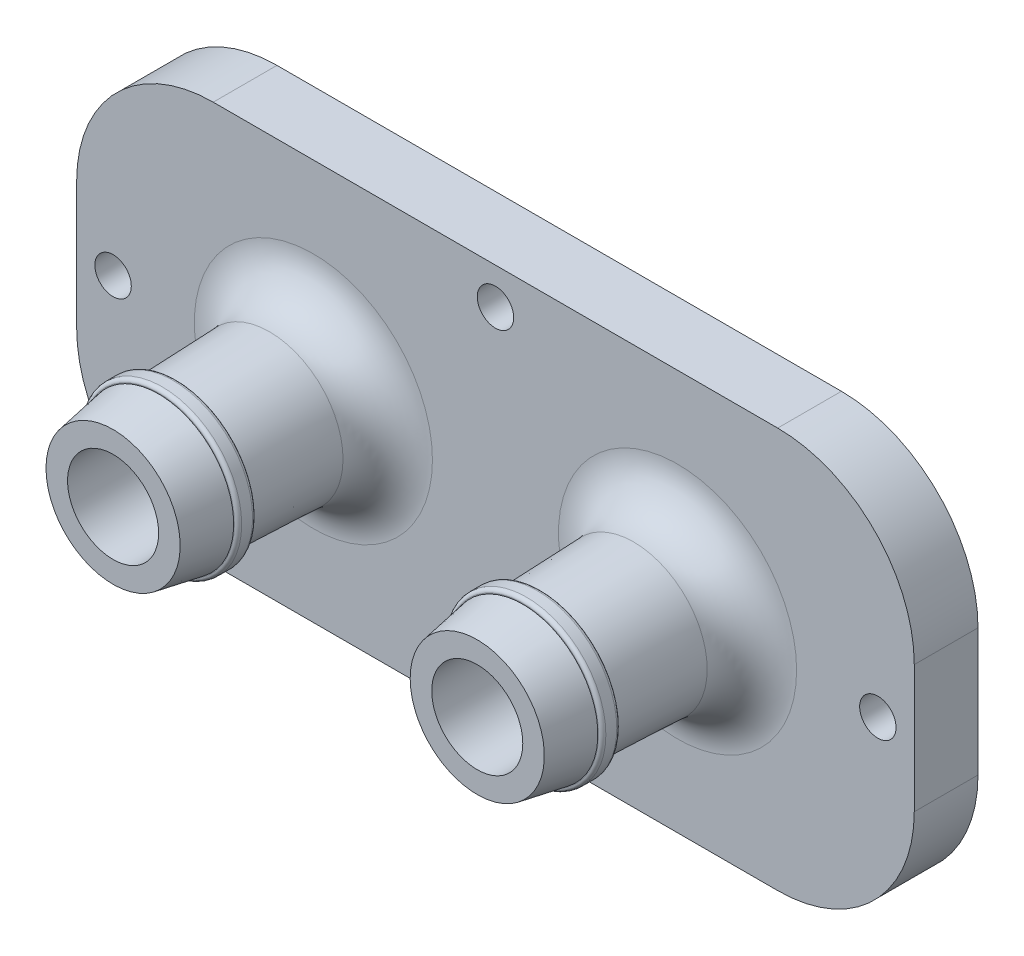
SolidWorks part; units mm, degrees
ref_plane "Front Plane" through (0, 0, 0) normal (0, 0, 1) x (1, 0, 0)
ref_plane "Top Plane" through (0, 0, 0) normal (0, 1, 0) x (1, 0, 0)
ref_plane "Right Plane" through (0, 0, 0) normal (1, 0, 0) x (0, 0, -1)
sketch "Sketch1" plane through (0, 0, 0) normal (0, 0, 1) x (1, 0, 0)
  line L0 (-38.0465, 0) -> (47.5349, 0) construction
  line L1 (0, 0) -> (0, 26.093) construction
  line L3 (-46, 22) -> (46, 22)
  line L4 (-46, 22) -> (-46, -22)
  line L5 (-46, -22) -> (46, -22)
  line L6 (46, 22) -> (46, -22)
  circle A0 centre (20, 0) radius 17
  circle A1 centre (-20, 0) radius 17
  point P9 (0, 0)
  point P14 (0, 0)
  dimension "D2" = 34
  dimension "D1" = 40
  dimension "D3" = 26
  dimension "D4" = 22
extrude "Boss-Extrude1" add sketch "Sketch1" along normal blind 4
fillet "Fillet1" radius 15 4 edges at (-46, -22, 2) (46, -22, 2) (46, 22, 2) (-46, 22, 2)
sketch "Sketch2" plane through (0, 0, 4) normal (0, 0, 1) x (1, 0, 0)
  line L8 (-46, 7) -> (-46, -7)
  line L9 (-31, -22) -> (31, -22)
  line L10 (46, -7) -> (46, 7)
  line L11 (31, 22) -> (-31, 22)
  line L12 (-46, 7) -> (-46, -7)
  line L13 (-31, -22) -> (31, -22)
  line L14 (46, -7) -> (46, 7)
  line L15 (31, 22) -> (-31, 22)
  circle A4 centre (-20, 0) radius 5
  circle A5 centre (-20, 0) radius 17 construction
  circle A6 centre (20, 0) radius 5
  circle A7 centre (20, 0) radius 17 construction
  arc A8 (-31, 22) -> (-46, 7) centre (-31, 7) ccw
  arc A9 (-46, -7) -> (-31, -22) centre (-31, -7) ccw
  arc A10 (31, -22) -> (46, -7) centre (31, -7) ccw
  arc A11 (46, 7) -> (31, 22) centre (31, 7) ccw
  arc A12 (-31, 22) -> (-46, 7) centre (-31, 7) ccw
  arc A13 (-46, -7) -> (-31, -22) centre (-31, -7) ccw
  arc A14 (31, -22) -> (46, -7) centre (31, -7) ccw
  arc A15 (46, 7) -> (31, 22) centre (31, 7) ccw
  dimension "D2" = 10
  dimension "D1" = 0
extrude "Boss-Extrude2" add sketch "Sketch2" along normal blind 3
sketch "Sketch3" plane through (0, 0, 7) normal (0, 0, 1) x (1, 0, 0)
  circle A0 centre (-20, 0) radius 7.25
  circle A1 centre (20, 0) radius 7.25
  circle A2 centre (20, 0) radius 5
  circle A3 centre (-20, 0) radius 5
  circle A4 centre (-20, 0) radius 5 construction
  point P9 (-20, -0.8455)
  dimension "D1" = 14.5
extrude "Boss-Extrude3" add sketch "Sketch3" along normal blind 15
chamfer "Chamfer1" distance 1 angle 88 2 edges at (-12.75, 0, 7) (27.25, 0, 7) first distance on face at (-12.75, 0, 7)
fillet "Fillet2" radius 2 2 edges at (-3, 0, 4) (37, 0, 4)
fillet "Fillet3" radius 10 2 edges at (-15, 0, 4) (25, 0, 4)
fillet "Fillet4" radius 5 2 edges at (28.25, 0, 7) (-11.75, 0, 7)
sketch "Sketch4" plane through (0, 0, 22) normal (0, 0, 1) x (1, 0, 0)
  circle A0 centre (-20, 0) radius 5
  circle A1 centre (-20, 0) radius 8.7262
  circle A2 centre (20, 0) radius 5
  circle A3 centre (20, 0) radius 8.7262
  circle A4 centre (20, 0) radius 7.7262 construction
  circle A5 centre (-20, 0) radius 5 construction
  circle A6 centre (20, 0) radius 5 construction
  dimension "D1" = 1
extrude "Boss-Extrude4" add sketch "Sketch4" along normal blind 2
sketch "Sketch6" plane through (0, 0, 24) normal (0, 0, 1) x (1, 0, 0)
  circle A0 centre (20, 0) radius 5
  circle A1 centre (20, 0) radius 7.25
  circle A2 centre (-20, 0) radius 7.25
  circle A3 centre (-20, 0) radius 5
  circle A4 centre (-20, 0) radius 5 construction
  dimension "D1" = 14.5
extrude "Boss-Extrude5" add sketch "Sketch6" along normal blind 5
fillet "Fillet5" radius 0.4 6 edges at (27.7262, 0, 22) (28.7262, 0, 22) (28.7262, 0, 24) (-12.2738, 0, 22) (-11.2738, 0, 22) (-11.2738, 0, 24)
chamfer "Chamfer2" distance 1 angle 80 2 edges at (27.25, 0, 24) (-12.75, 0, 24) first distance on face at (28.3262, 0, 24) first distance on face at (-11.6738, 0, 24)
sketch "Sketch8" plane through (0, 0, 7) normal (0, 0, 1) x (1, 0, 0)
  line L0 (0, 0) -> (0, 39.11) construction
  line L1 (0, 0) -> (65.4286, 0) construction
  circle A0 centre (0, 18) radius 2
  circle A1 centre (0, -18) radius 2
  circle A2 centre (42, 0) radius 2
  circle A3 centre (-42, 0) radius 2
  point P11 (0, 0)
  point P13 (0, 0)
  dimension "D1" = 4
  dimension "D2" = 84
  dimension "D3" = 36
extrude "Cut-Extrude1" cut sketch "Sketch8" against normal through all
